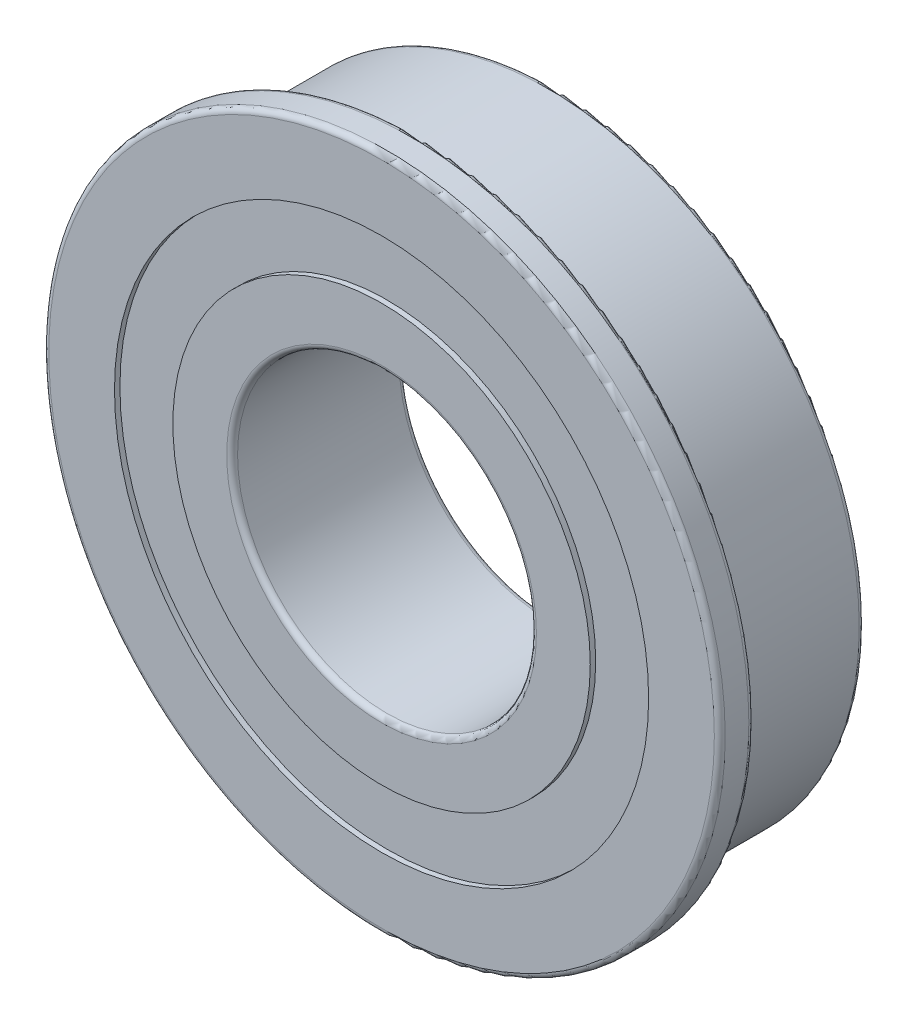
SolidWorks part; units mm, degrees
ref_plane "Front" through (0, 0, 0) normal (0, 0, 1) x (1, 0, 0)
ref_plane "Top" through (0, 0, 0) normal (0, 1, 0) x (1, 0, 0)
ref_plane "Right" through (0, 0, 0) normal (1, 0, 0) x (0, 0, -1)
sketch "Sketch1" plane through (0, 0, 0) normal (0, 1, 0) x (1, 0, 0)
  line L0 (14.0375, 3.9688) -> (12.2875, 3.9688)
  line L1 (12.2875, 3.9688) -> (12.2875, 3.7188)
  line L2 (12.2875, 3.7188) -> (9.602, 3.7188)
  line L3 (9.602, 3.7188) -> (9.602, 3.9688)
  line L4 (9.602, 3.9688) -> (7.125, 3.9688)
  line L5 (6.875, 3.7188) -> (6.875, -3.7188)
  line L6 (7.125, -3.9688) -> (9.602, -3.9688)
  line L7 (9.602, -3.9688) -> (9.602, -3.7188)
  line L8 (9.602, -3.7188) -> (12.2875, -3.7188)
  line L9 (12.2875, -3.7188) -> (12.2875, -3.9688)
  line L10 (12.2875, -3.9688) -> (15.31, -3.9688)
  line L11 (15.56, -3.7188) -> (15.56, -2.6313)
  line L12 (15.31, -2.3812) -> (14.2875, -2.3812)
  line L13 (14.071, -2.0062) -> (14.2875, -1.6312)
  line L14 (14.2875, -1.6312) -> (14.2875, 3.7188)
  line L15 (0, 3.97) -> (0, -3.97) construction
  arc A0 (7.125, 3.9688) -> (6.875, 3.7188) centre (7.125, 3.7188) ccw
  arc A1 (6.875, -3.7188) -> (7.125, -3.9688) centre (7.125, -3.7188) ccw
  arc A2 (15.31, -3.9688) -> (15.56, -3.7188) centre (15.31, -3.7188) ccw
  arc A3 (15.56, -2.6313) -> (15.31, -2.3812) centre (15.31, -2.6313) ccw
  arc A4 (14.2875, -2.3812) -> (14.071, -2.0062) centre (14.2875, -2.1312) cw
  arc A5 (14.2875, 3.7188) -> (14.0375, 3.9688) centre (14.0375, 3.7188) ccw
revolve "Revolve1" add sketch "Sketch1" angle 360 about L15 reverse direction yes
